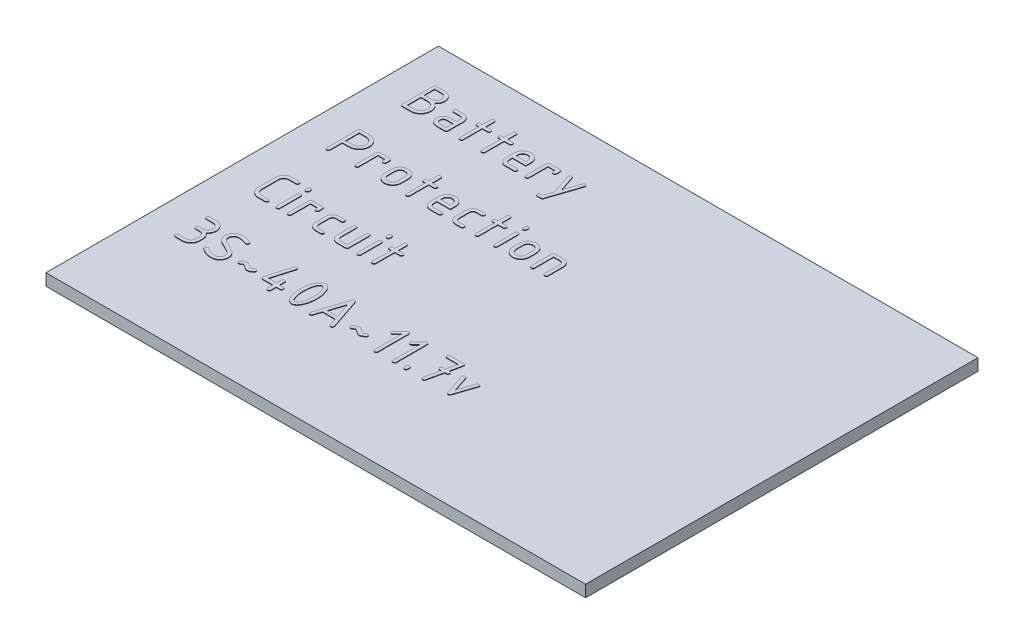
SolidWorks part; units mm, degrees
ref_plane "Front Plane" through (0, 0, 0) normal (0, 0, 1) x (1, 0, 0)
ref_plane "Top Plane" through (0, 0, 0) normal (0, 1, 0) x (1, 0, 0)
ref_plane "Right Plane" through (0, 0, 0) normal (1, 0, 0) x (0, 0, -1)
sketch "Sketch1" plane through (0, 0, 0) normal (0, 1, 0) x (1, 0, 0)
  line L1 (-27.5, -20) -> (27.5, -20)
  line L2 (-27.5, -20) -> (-27.5, 20)
  line L3 (-27.5, 20) -> (27.5, 20)
  line L4 (27.5, -20) -> (27.5, 20)
  line L5 (-27.5, -20) -> (27.5, 20) construction
  line L6 (-27.5, 20) -> (27.5, -20) construction
  point P0 (0, 0)
  dimension "D1" = 40
  dimension "D2" = 55
extrude "boss-PCB" add sketch "Sketch1" along normal blind 1.2
sketch "Sketch2" plane through (0, 1.2, 0) normal (0, 1, 0) x (1, 0, 0)
  text T0 "Battery\r\nProtection\r\nCircuit\r\n3S~40A~11.7v" font "DS ISO 1" height 3.5
extrude "boss-Text" add sketch "Sketch2" along normal blind 0.05
